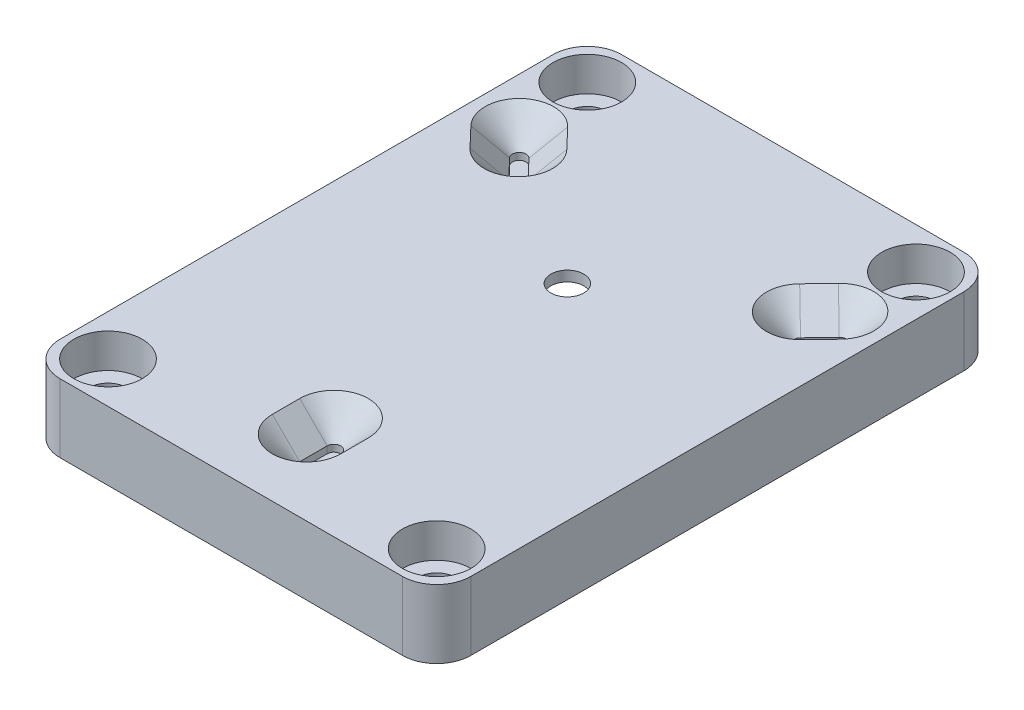
SolidWorks part; units mm, degrees
ref_plane "Front Plane" through (0, 0, 0) normal (0, 0, 1) x (1, 0, 0)
ref_plane "Top Plane" through (0, 0, 0) normal (0, 1, 0) x (1, 0, 0)
ref_plane "Right Plane" through (0, 0, 0) normal (1, 0, 0) x (0, 0, -1)
sketch "Sketch1" plane through (0, 0, 0) normal (0, 1, 0) x (1, 0, 0)
  line L1 (-30, 41) -> (30, 41)
  line L2 (-30, 41) -> (-30, -41)
  line L3 (-30, -41) -> (30, -41)
  line L4 (30, 41) -> (30, -41)
  line L5 (-30, 41) -> (30, -41) construction
  line L6 (-30, -41) -> (30, 41) construction
  point P0 (0, 0)
  dimension "D1" = 60
  dimension "D2" = 82
extrude "Boss-Extrude1" add sketch "Sketch1" along normal blind 10
sketch "Sketch2" plane through (0, 10, 0) normal (0, 1, 0) x (1, 0, 0)
  line L6 (-17.3812, 23) -> (-19.6906, 27)
  line L7 (-19.6906, 19) -> (-17.3812, 23)
  line L8 (-24.3094, 19) -> (-19.6906, 19)
  line L9 (-26.6188, 23) -> (-24.3094, 19)
  line L10 (-24.3094, 27) -> (-26.6188, 23)
  line L11 (-19.6906, 27) -> (-24.3094, 27)
  line L12 (-17.3812, 23) -> (-19.6906, 27)
  line L13 (-19.6906, 19) -> (-17.3812, 23)
  line L14 (-24.3094, 19) -> (-19.6906, 19)
  line L15 (-26.6188, 23) -> (-24.3094, 19)
  line L16 (-24.3094, 27) -> (-26.6188, 23)
  line L17 (-19.6906, 27) -> (-24.3094, 27)
  line L18 (-4, -30.3094) -> (0, -32.6188)
  line L19 (-4, -25.6906) -> (-4, -30.3094)
  line L20 (0, -23.3812) -> (-4, -25.6906)
  line L21 (4, -25.6906) -> (0, -23.3812)
  line L22 (4, -30.3094) -> (4, -25.6906)
  line L23 (0, -32.6188) -> (4, -30.3094)
  line L24 (-4, -30.3094) -> (0, -32.6188)
  line L25 (-4, -25.6906) -> (-4, -30.3094)
  line L26 (0, -23.3812) -> (-4, -25.6906)
  line L27 (4, -25.6906) -> (0, -23.3812)
  line L28 (4, -30.3094) -> (4, -25.6906)
  line L29 (0, -32.6188) -> (4, -30.3094)
  line L30 (17.3812, 23) -> (19.6906, 19)
  line L31 (19.6906, 27) -> (17.3812, 23)
  line L32 (24.3094, 27) -> (19.6906, 27)
  line L33 (26.6188, 23) -> (24.3094, 27)
  line L34 (24.3094, 19) -> (26.6188, 23)
  line L35 (19.6906, 19) -> (24.3094, 19)
  line L36 (17.3812, 23) -> (19.6906, 19)
  line L37 (19.6906, 27) -> (17.3812, 23)
  line L38 (24.3094, 27) -> (19.6906, 27)
  line L39 (26.6188, 23) -> (24.3094, 27)
  line L40 (24.3094, 19) -> (26.6188, 23)
  line L41 (19.6906, 19) -> (24.3094, 19)
  dimension "D1" = 0
  dimension "D2" = 0
  dimension "D3" = 0
sketch "Sketch3" plane through (0, 10, 0) normal (0, 1, 0) x (1, 0, 0)
  line L0 (0, 0) -> (22, 23) construction
  line L1 (0, 0) -> (-22, 23) construction
  line L2 (-24.3094, 19) -> (-19.6906, 27) construction
  line L3 (19.6906, 27) -> (24.3094, 19) construction
  line L4 (-4, -30.3094) -> (4, -25.6906) construction
  line L5 (0, 0) -> (0, -28) construction
  line L6 (-23.3824, 24.4453) -> (-20.6176, 21.5547) construction
  line L7 (-22.6598, 25.1365) -> (-19.8949, 22.2459)
  line L8 (-24.1051, 23.7541) -> (-21.3402, 20.8635)
  line L9 (23.3824, 24.4453) -> (20.6176, 21.5547) construction
  line L10 (24.1051, 23.7541) -> (21.3402, 20.8635)
  line L11 (22.6598, 25.1365) -> (19.8949, 22.2459)
  line L12 (0, -30) -> (0, -26) construction
  line L13 (-1, -30) -> (-1, -26)
  line L14 (1, -30) -> (1, -26)
  arc A0 (-22.6598, 25.1365) -> (-24.1051, 23.7541) centre (-23.3824, 24.4453) ccw
  arc A1 (-21.3402, 20.8635) -> (-19.8949, 22.2459) centre (-20.6176, 21.5547) ccw
  arc A2 (24.1051, 23.7541) -> (22.6598, 25.1365) centre (23.3824, 24.4453) ccw
  arc A3 (19.8949, 22.2459) -> (21.3402, 20.8635) centre (20.6176, 21.5547) ccw
  arc A4 (-1, -30) -> (1, -30) centre (0, -30) ccw
  arc A5 (1, -26) -> (-1, -26) centre (0, -26) ccw
  point P19 (-22, 23)
  point P25 (22, 23)
  point P32 (0, -28)
  dimension "D2" = 1
  dimension "D1" = 4
extrude "Cut-Extrude1" cut sketch "Sketch3" against normal blind 5
chamfer "Chamfer1" distance 4 angle 45 12 edges at (-22.7226, 10, -22.3088) (-19.9263, 10, -20.8321) (-24.0737, 10, -25.1679) (-21.2774, 10, -23.6912) (-1, 10, 28) (0, 10, 31) (0, 10, 25) (1, 10, 28) (21.2774, 10, -23.6912) (19.9263, 10, -20.8321) (24.0737, 10, -25.1679) (22.7226, 10, -22.3088)
sketch "Sketch4" plane through (0, 10, 0) normal (0, 1, 0) x (1, 0, 0)
  circle A0 centre (0, 8.08) radius 2.4 construction
  circle A1 centre (0, 8.08) radius 2.4
extrude "Cut-Extrude2" cut sketch "Sketch4" against normal through all contours A1
sketch "Sketch5" plane through (0, 10, 0) normal (0, 1, 0) x (1, 0, 0)
  circle A0 centre (0, 8.08) radius 15
  circle A1 centre (0, 8.08) radius 2.4 construction
  point P2 (0, 0)
  dimension "D1" = 30
extrude "Cut-Extrude3" cut sketch "Sketch5" against normal through all from offset 1.5 offset against normal yes
sketch "Sketch6" plane through (0, 10, 0) normal (0, 1, 0) x (1, 0, 0)
  line L8 (24, -35) -> (24, 35)
  line L9 (24, 35) -> (-24, 35)
  line L10 (-24, 35) -> (-24, -35)
  line L11 (-24, -35) -> (24, -35)
  line L12 (24, -35) -> (24, 35) construction
  line L13 (24, 35) -> (-24, 35) construction
  line L14 (-24, 35) -> (-24, -35) construction
  line L15 (-24, -35) -> (24, -35) construction
  dimension "D1" = 6
hole_wizard "CBORE for M5 SHCS1" positions "Sketch7" profile "Sketch8" counterbore size "M5" standard "ANSI Metric" end condition through all
sketch "Sketch7" plane through (0, 10, 0) normal (0, 1, 0) x (1, 0, 0)
  point P0 (-24, 35)
  point P3 (24, 35)
  point P6 (24, -35)
  point P9 (-24, -35)
sketch "Sketch8" plane through (-24, 10, -35) normal (1, 0, 0) x (0, 0, 1)
  line L0 (0, 0) -> (0, 10)
  line L1 (0, 10) -> (2.75, 10)
  line L3 (2.75, 10) -> (2.75, 5)
  line L4 (2.75, 5) -> (5, 5)
  line L5 (5, 5) -> (5, 0)
  line L7 (5, 0) -> (0, 0)
  line L11 (0, -6.35) -> (0, 107.95) construction
  dimension "Thru Hole Dia." = 5.5
  dimension "Thru Hole Depth" = 10
  dimension "C'Bore Dia." = 10
  dimension "C'Bore Depth" = 5
fillet "Fillet1" radius 5 4 edges at (30, 5, -41) (30, 5, 41) (-30, 5, 41) (-30, 5, -41)
sketch "Sketch9" plane through (0, 0, 0) normal (0, -1, 0) x (1, 0, 0)
  circle A0 centre (0, 6.92) radius 0.35
  circle A1 centre (0, -8.08) radius 15 construction
  circle A2 centre (12.9904, -15.58) radius 0.35
  circle A3 centre (-12.9904, -15.58) radius 0.35
  point P7 (0, 0)
  point P12 (0, -8.08)
  dimension "D1" = 0.7
  dimension "D2" = 3
extrude "Boss-Extrude2" add sketch "Sketch9" against normal up to next
